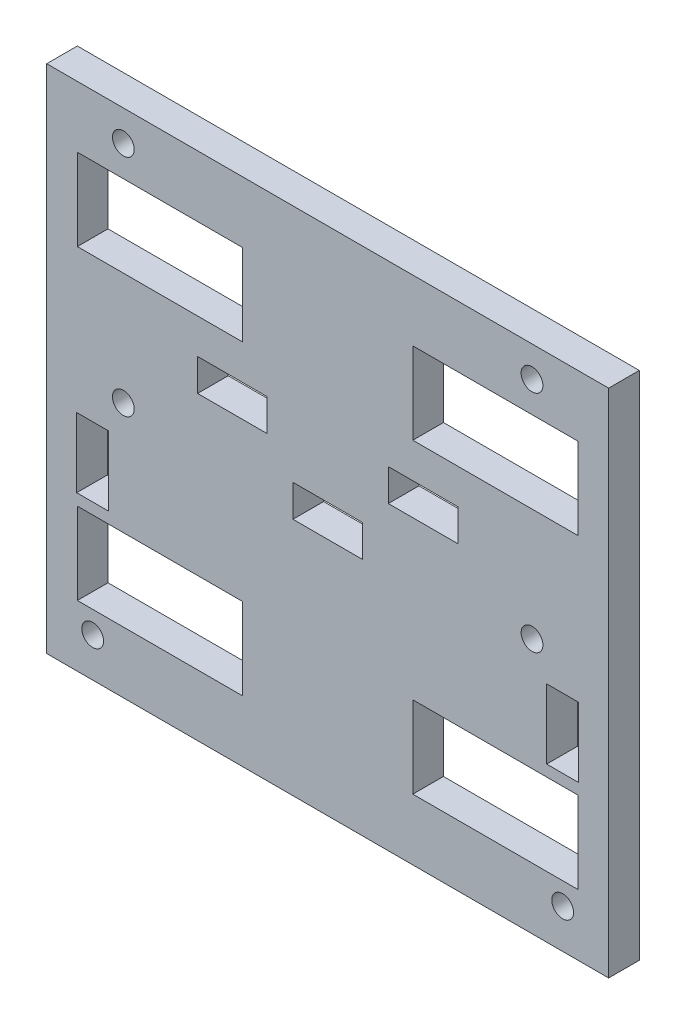
SolidWorks part; units mm, degrees
ref_plane "Front Plane" through (0, 0, 0) normal (0, 0, 1) x (1, 0, 0)
ref_plane "Top Plane" through (0, 0, 0) normal (0, 1, 0) x (1, 0, 0)
ref_plane "Right Plane" through (0, 0, 0) normal (1, 0, 0) x (0, 0, -1)
sketch "Sketch1" plane through (0, 0, 0) normal (0, 0, 1) x (1, 0, 0)
  line L0 (0, -37.5) -> (0, 37.5) construction
  line L1 (-41.25, -37.5) -> (41.25, -37.5)
  line L2 (-41.25, -37.5) -> (-41.25, 37.5)
  line L3 (-41.25, 37.5) -> (41.25, 37.5)
  line L4 (41.25, -37.5) -> (41.25, 37.5)
  line L5 (-41.25, -37.5) -> (41.25, 37.5) construction
  line L6 (-41.25, 37.5) -> (41.25, -37.5) construction
  line L7 (-41.25, 0) -> (41.25, 0) construction
  line L8 (-41.25, 22.5) -> (41.25, 22.5) construction
  line L9 (36.75, 16.5) -> (12.5, 28.5) construction
  line L10 (-36.75, 28.5) -> (-12.5, 28.5)
  line L11 (-36.75, 28.5) -> (-36.75, 16.5)
  line L12 (-36.75, 16.5) -> (-12.5, 16.5)
  line L13 (-12.5, 28.5) -> (-12.5, 16.5)
  line L14 (-36.75, 28.5) -> (-12.5, 16.5) construction
  line L15 (-36.75, 16.5) -> (-12.5, 28.5) construction
  line L16 (36.75, 28.5) -> (12.5, 16.5) construction
  line L17 (12.5, 28.5) -> (12.5, 16.5)
  line L18 (36.75, 16.5) -> (12.5, 16.5)
  line L19 (36.75, 28.5) -> (36.75, 16.5)
  line L20 (36.75, 28.5) -> (12.5, 28.5)
  line L21 (36.75, -28.5) -> (12.5, -16.5) construction
  line L22 (-36.75, -16.5) -> (-12.5, -28.5) construction
  line L23 (-36.75, -28.5) -> (-12.5, -16.5) construction
  line L24 (36.75, -16.5) -> (12.5, -28.5) construction
  line L25 (36.75, -28.5) -> (12.5, -28.5)
  line L26 (36.75, -28.5) -> (36.75, -16.5)
  line L27 (36.75, -16.5) -> (12.5, -16.5)
  line L28 (12.5, -28.5) -> (12.5, -16.5)
  line L29 (-12.5, -28.5) -> (-12.5, -16.5)
  line L30 (-36.75, -16.5) -> (-12.5, -16.5)
  line L31 (-36.75, -28.5) -> (-36.75, -16.5)
  line L32 (-36.75, -28.5) -> (-12.5, -28.5)
  point P0 (0, 0)
  point P12 (-24.625, 22.5)
  point P21 (24.625, 22.5)
  point P30 (24.625, -22.5)
  point P31 (-24.625, -22.5)
  dimension "D1" = 82.5
  dimension "D2" = 75
  dimension "D3" = 22.5
  dimension "D4" = 24.25
  dimension "D5" = 12
  dimension "D6" = 12.5
extrude "Boss-Extrude1" add sketch "Sketch1" along normal blind 4.5
sketch "Sketch2" plane through (0, 0, 4.5) normal (0, 0, 1) x (1, 0, 0)
  line L0 (0, -37.5) -> (0, 37.5) construction
  line L1 (-41.25, -37.5) -> (41.25, -37.5) construction
  line L2 (41.25, 37.5) -> (-41.25, 37.5) construction
  line L3 (-41.25, 0) -> (41.25, 0) construction
  line L4 (-41.25, 37.5) -> (-41.25, -37.5) construction
  line L5 (41.25, -37.5) -> (41.25, 37.5) construction
  line L6 (-30, 0) -> (30, 0) construction
  circle A0 centre (-30, 33) radius 1.6
  circle A1 centre (30, 33) radius 1.6
  circle A2 centre (30, 0) radius 1.6
  circle A3 centre (-30, 0) radius 1.6
  dimension "D1" = 3.2
  dimension "D7" = 3.2
  dimension "D8" = 3.2
  dimension "D2" = 30
  dimension "D3" = 33
  dimension "D4" = 60
  dimension "D5" = 30
  dimension "D6" = 0
extrude "screwHoles" cut sketch "Sketch2" against normal through all
sketch "Sketch3" plane through (0, 0, 4.5) normal (0, 0, 1) x (1, 0, 0)
  line L0 (-41.25, 9) -> (26.0486, 9) construction
  line L1 (-41.25, 37.5) -> (-41.25, -37.5) construction
  line L3 (0, 37.5) -> (0, -37.5) construction
  line L4 (41.25, 37.5) -> (-41.25, 37.5) construction
  line L5 (-41.25, -37.5) -> (41.25, -37.5) construction
  line L6 (19.1, 6.65) -> (8.9, 11.35) construction
  line L7 (-19.1, 11.35) -> (-8.9, 11.35)
  line L8 (-19.1, 11.35) -> (-19.1, 6.65)
  line L9 (-19.1, 6.65) -> (-8.9, 6.65)
  line L10 (-8.9, 11.35) -> (-8.9, 6.65)
  line L11 (-19.1, 11.35) -> (-8.9, 6.65) construction
  line L12 (-19.1, 6.65) -> (-8.9, 11.35) construction
  line L13 (19.1, 11.35) -> (8.9, 6.65) construction
  line L14 (8.9, 11.35) -> (8.9, 6.65)
  line L15 (19.1, 6.65) -> (8.9, 6.65)
  line L16 (19.1, 11.35) -> (19.1, 6.65)
  line L17 (19.1, 11.35) -> (8.9, 11.35)
  line L18 (-41.25, 37.5) -> (-41.25, -37.5) construction
  point P2 (-41.25, 0)
  point P12 (-14, 9)
  point P21 (14, 9)
  dimension "D1" = 10.2
  dimension "D2" = 4.7
  dimension "D3" = 14
  dimension "D4" = 9
extrude "BeltClamp" cut sketch "Sketch3" against normal through all
sketch "Sketch4" plane through (0, 0, 4.5) normal (0, 0, 1) x (1, 0, 0)
  line L0 (-41.25, 0) -> (41.25, 0) construction
  line L1 (-41.25, 37.5) -> (-41.25, -37.5) construction
  line L2 (41.25, -37.5) -> (41.25, 37.5) construction
  line L4 (-5.1, 2.35) -> (5.1, 2.35)
  line L5 (-5.1, 2.35) -> (-5.1, -2.35)
  line L6 (-5.1, -2.35) -> (5.1, -2.35)
  line L7 (5.1, 2.35) -> (5.1, -2.35)
  line L8 (-5.1, 2.35) -> (5.1, -2.35) construction
  line L9 (-5.1, -2.35) -> (5.1, 2.35) construction
  circle A0 centre (-30, 0) radius 1.6 construction
  point P6 (0, 0)
  dimension "D1" = 10.2
  dimension "D2" = 4.7
  dimension "D3" = 0
extrude "Cut-Extrude3" cut sketch "Sketch4" against normal through all
sketch "Sketch5" plane through (0, 0, 4.5) normal (0, 0, 1) x (1, 0, 0)
  line L0 (-41.25, -9.75) -> (41.25, -9.75) construction
  line L1 (-41.25, 37.5) -> (-41.25, -37.5) construction
  line L2 (41.25, -37.5) -> (41.25, 37.5) construction
  line L3 (5.1, -2.35) -> (5.1, 2.35) construction
  line L4 (0, -37.5) -> (0, 37.5) construction
  line L5 (-41.25, -37.5) -> (41.25, -37.5) construction
  line L6 (41.25, 37.5) -> (-41.25, 37.5) construction
  line L7 (-32.15, -14.85) -> (-36.85, -4.65) construction
  line L8 (32.15, -4.65) -> (36.85, -4.65)
  line L9 (32.15, -4.65) -> (32.15, -14.85)
  line L10 (32.15, -14.85) -> (36.85, -14.85)
  line L11 (36.85, -4.65) -> (36.85, -14.85)
  line L12 (32.15, -4.65) -> (36.85, -14.85) construction
  line L13 (32.15, -14.85) -> (36.85, -4.65) construction
  line L14 (-32.15, -4.65) -> (-36.85, -14.85) construction
  line L15 (-36.85, -4.65) -> (-36.85, -14.85)
  line L16 (-32.15, -14.85) -> (-36.85, -14.85)
  line L17 (-32.15, -4.65) -> (-32.15, -14.85)
  line L18 (-32.15, -4.65) -> (-36.85, -4.65)
  line L19 (34.5, -9.75) -> (34.5, -37.5) construction
  line L20 (-34.5, -9.75) -> (-34.5, -37.5) construction
  circle A0 centre (34.5, -31.75) radius 1.6
  circle A1 centre (-34.5, -31.75) radius 1.6
  point P6 (5.1, 0)
  point P15 (34.5, -9.75)
  point P24 (-34.5, -9.75)
  dimension "D5" = 3.2
  dimension "D1" = 9.75
  dimension "D2" = 10.2
  dimension "D3" = 4.7
  dimension "D4" = 34.5
  dimension "D6" = 22
extrude "Cut-Extrude4" cut sketch "Sketch5" against normal through all
sketch "Sketch6" plane through (0, 0, 4.5) normal (0, 0, 1) x (1, 0, 0)
  line L0 (-36.85, -9.75) -> (36.85, -9.75) construction
  line L1 (-36.85, -4.65) -> (-36.85, -14.85) construction
  line L2 (36.85, -14.85) -> (36.85, -4.65) construction
  line L3 (0, -2.35) -> (0, -37.5) construction
  line L4 (-5.1, -2.35) -> (5.1, -2.35) construction
  line L5 (-41.25, -37.5) -> (41.25, -37.5) construction
  line L6 (34.5, -14.85) -> (34.5, -4.65) construction
  line L7 (32.15, -14.85) -> (36.85, -14.85) construction
  line L8 (36.85, -4.65) -> (32.15, -4.65) construction
  line L9 (32.15, -4.65) -> (32.15, -14.85) construction
  line L10 (31.15, -15.85) -> (37.85, -15.85)
  line L11 (31.15, -15.85) -> (31.15, -3.65)
  line L12 (31.15, -3.65) -> (37.85, -3.65)
  line L13 (37.85, -15.85) -> (37.85, -3.65)
  line L14 (31.15, -15.85) -> (37.85, -3.65) construction
  line L15 (31.15, -3.65) -> (37.85, -15.85) construction
  line L16 (-31.15, -3.65) -> (-37.85, -15.85) construction
  line L17 (-31.15, -15.85) -> (-37.85, -3.65) construction
  line L18 (-34.5, -14.85) -> (-34.5, -4.65) construction
  line L19 (-37.85, -15.85) -> (-37.85, -3.65)
  line L20 (-31.15, -3.65) -> (-37.85, -3.65)
  line L21 (-31.15, -15.85) -> (-31.15, -3.65)
  line L22 (-31.15, -15.85) -> (-37.85, -15.85)
  circle A0 centre (34.5, -9.75) radius 1.6
  circle A1 centre (-34.5, -9.75) radius 1.6
  point P18 (34.5, -9.75)
  dimension "D3" = 3.2
  dimension "D1" = 1
  dimension "D2" = 1
extrude "FrontToRear1" [suppressed] add sketch "Sketch6" against normal up to surface (4.5 mm away) up to face at (-36.1, -31.75, 0)
sketch "Sketch7" plane through (0, 0, 4.5) normal (0, 0, 1) x (1, 0, 0)
  line L0 (5.1, 2.35) -> (-5.1, 2.35) construction
  line L1 (-35, -3.35) -> (35, -3.35)
  line L2 (-35, -3.35) -> (-35, 3.35)
  line L3 (-35, 3.35) -> (35, 3.35)
  line L4 (35, -3.35) -> (35, 3.35)
  line L5 (-35, -3.35) -> (35, 3.35) construction
  line L6 (-35, 3.35) -> (35, -3.35) construction
  circle A0 centre (30, 0) radius 1.6 construction
  point P0 (0, 0)
  dimension "D1" = 1
  dimension "D2" = 5
extrude "FrontToRear2" [suppressed] add sketch "Sketch7" against normal through all
equation "\"X-ROD-SPACING\"=45"
equation "\"Y-ROD-SPACING\"=75"
equation "\"Z-ROD-SPACING\"=17.5"
equation "\"Y-BED-OFFSET\"=2"
equation "\"Y-BED-ROD-INSET\"=3.5"
equation "\"Y-BED-SCREW-SPACING\"=209"
equation "\"Y-BED-SCREW-CUTOUT-SLOT-HEIGHT\"=1"
equation "\"T-SLOT-NUT-FILLET-RADIUS\"=0.25"
equation "\"T-SLOT-SCREW-SHAFT-RADIUS\"=1.75"
equation "\"T-SLOT-SCREW-SHAFT-CUTOUT-LENGTH\"=10.5"
equation "\"T-SLOT-NUT-DEPTH\"=4.2"
equation "\"T-SLOT-NUT-WIDTH\"=3"
equation "\"T-SLOT-NUT-END-DISTANCE\"=8"
equation "\"ACRYLIC-THICKNESS\"=10"
equation "\"ACRYLIC-THICKNESS2\"=4.5"
equation "\"ACRYLIC-TAB-CUTOUT-SIZE\"=\"ACRYLIC-THICKNESS\"+\"ACRYLIC-TAB-TOLERANCE\"*2"
equation "\"ACRYLIC-TAB-WIDTH\"=\"ACRYLIC-THICKNESS\""
equation "\"ACRYLIC-M3-HOLE\"=3.2"
equation "\"SMOOTHROD-CAP-SCREW-DISTANCE\"=20"
equation "\"FRAME-WIDTH-INNER\"=370"
equation "\"NEMA17-HOLE-SPACING\"=31"
equation "\"NEMA17-CENTRAL-CUTOUT\"=22.5"
equation "\"Z-BRACKET-REACH\"=55"
equation "\"Z-ROD-INSET\"=16"
equation "\"TOP-BRACKET-SPACING\"=40"
equation "\"SMOOTHROD-X-LENGTH\"=350"
equation "\"SMOOTHROD-Y-LENGTH\"=350"
equation "\"SMOOTHROD-Z-LENGTH\"=350"
equation "\"SMOOTHROD-TIGHTENING-HEADROOM\"=1"
equation "\"LEADSCREW-Z-LENGTH\"=300"
equation "\"SCREW-LENGTH-FRAME\"=\"ACRYLIC-THICKNESS\" + 10"
equation "\"SCREW-LENGTH-MOTOR\"=\"ACRYLIC-THICKNESS\" + 5"
equation "\"SCREW-HEAD-RADIUS\"=6"
equation "\"PRINTED-X-SMOOTHROD-DIAMETER\"=8.2"
equation "\"PRINTED-X-SMOOTHROD-CUTOUT\"=10"
equation "\"PRINTED-X-BASE-HEIGHT\"=10"
equation "\"PRINTED-LM8UU-CUTOUT-SIZE\"=16"
equation "\"PRINTED-LM8UU-CUTOUT-LENGTH\"=24.5"
equation "\"PRINTED-X-IDLER-HEIGHT\"=16"
equation "\"PSU-MOUNTING-WIDTH\"=95"
equation "\"PSU-MOUNTING-HEIGHT\"=177"
equation "\"Y-BELT-TO-ROD-DISTANCE\"=20"
equation "\"SPOOL-HOLDER-ROD-SPACING\"=150"
equation "\"D3@Sketch1\"=\"X-ROD-SPACING\"/2"
equation "\"D4@Sketch1\"=\"ACRYLIC-X-CARRIAGE-LM8UU-CUTOUT-WIDTH\""
equation "\"D1@Boss-Extrude1\"=\"ACRYLIC-THICKNESS2\""
equation "\"D1@Sketch2\"=\"ACRYLIC-M3-HOLE\""
equation "\"D1@Sketch3\"=\"ACRYLIC-TAB-CUTOUT-SIZE\""
equation "\"D2@Sketch3\"=\"ACRYLIC-THICKNESS2\"+\"ACRYLIC-TAB-TOLERANCE\"*2"
equation "\"ACRYLIC-X-CARRIAGE-WIDTH\"=55"
equation "\"ACRYLIC-X-CARRIAGE-HEIGHT\"=75"
equation "\"D1@Sketch1\"=\"ACRYLIC-X-CARRIAGE-WIDTH\"*1.5"
equation "\"D2@Sketch1\"=\"ACRYLIC-X-CARRIAGE-HEIGHT\""
equation "\"ACRYLIC-X-CARRIAGE-CENTER-TAB-SPACING\"=14"
equation "\"D3@Sketch3\"=\"ACRYLIC-X-CARRIAGE-CENTER-TAB-SPACING\""
equation "\"SCREW-LENGTH-EXTRUDER\"=28"
equation "\"ACRYLIC-X-CARRIAGE-SCREW-SPACING-X\"=15"
equation "\"ACRYLIC-X-CARRIAGE-SCREW-SPACING-Y\"=33"
equation "\"D2@Sketch2\"=\"ACRYLIC-X-CARRIAGE-SCREW-SPACING-X\"*2"
equation "\"D3@Sketch2\"=\"ACRYLIC-X-CARRIAGE-SCREW-SPACING-Y\""
equation "\"D1@Sketch4\"=\"ACRYLIC-TAB-CUTOUT-SIZE\""
equation "\"D2@Sketch4\"=\"ACRYLIC-THICKNESS2\"+\"ACRYLIC-TAB-TOLERANCE\"*2"
equation "\"D2@Sketch5\"=\"ACRYLIC-TAB-CUTOUT-SIZE\""
equation "\"D3@Sketch5\"=\"ACRYLIC-THICKNESS2\"+\"ACRYLIC-TAB-TOLERANCE\"*2"
equation "\"ACRYLIC-X-CARRIAGE-EXTRUDER-SHELF-DEPTH\"=\"ACRYLIC-X-CARRIAGE-EXTRUDER-OFFSET\" + 30"
equation "\"ACRYLIC-X-CARRIAGE-EXTRUDER-BRACE-SPACING\"=23"
equation "\"D4@Sketch5\"=\"ACRYLIC-X-CARRIAGE-EXTRUDER-BRACE-SPACING\"*1.5"
equation "\"D1@Sketch5\"=\"ACRYLIC-THICKNESS2\"/2 + 7.5"
equation "\"D4@Sketch2\"=\"ACRYLIC-X-CARRIAGE-SCREW-SPACING-X\"*4"
equation "\"D5@Sketch2\"=\"ACRYLIC-X-CARRIAGE-SCREW-SPACING-X\"*2"
equation "\"D7@Sketch2\"=\"ACRYLIC-M3-HOLE\""
equation "\"D8@Sketch2\"=\"ACRYLIC-M3-HOLE\""
equation "\"ACRYLIC-X-CARRIAGE-LM8UU-CUTOUT-WIDTH\"=24.25"
equation "\"ACRYLIC-TAB-TOLERANCE\"=.1"
equation "\"ACRYLIC-X-CARRIAGE-EXTRUDER-OFFSET\"=26"
equation "\"ACRYLIC-X-CARRIAGE-EXTRUDER-ANGLE\"=90"
equation "\"ACRYLIC-X-CARRIAGE-EXTRUDER-BRACE-TAB-OFFSET\"=20"
equation "\"ACRYLIC-X-CARRIAGE-EXTRUDER-BRACE-HEIGHT\"=35"
equation "\"ACRYLIC-X-CARRIAGE-EXTRUDER-BRACE-SCREW-SPACING\"=22"
equation "\"D5@Sketch5\"=\"ACRYLIC-M3-HOLE\""
equation "\"D3@Sketch6\"=\"ACRYLIC-M3-HOLE\""
